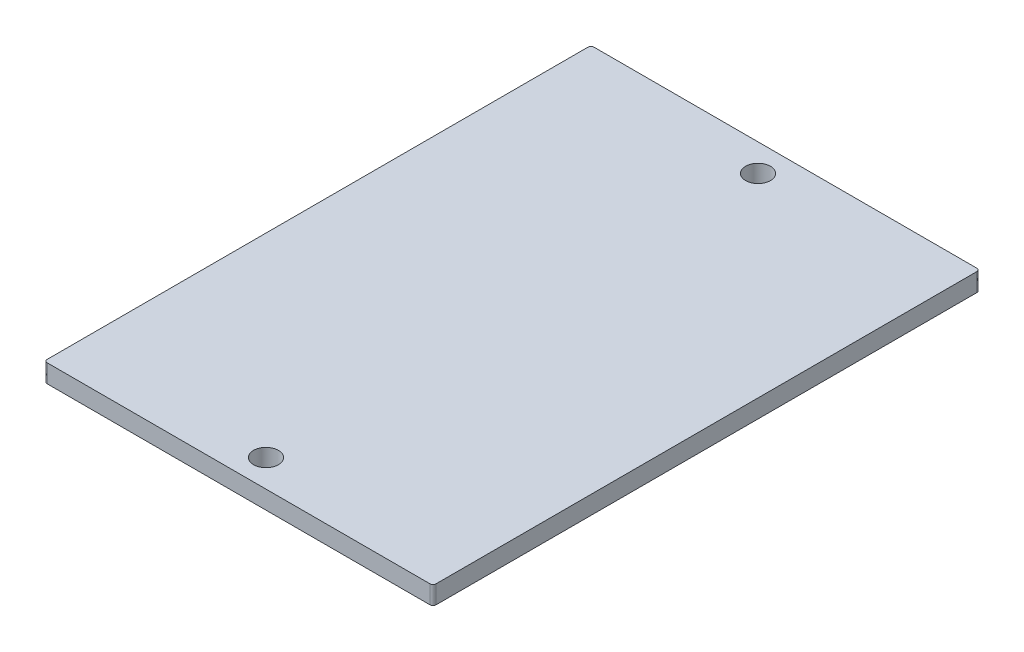
SolidWorks part; units mm, degrees
material "ABS"
ref_plane "Front Plane" through (0, 0, 0) normal (0, 0, 1) x (1, 0, 0)
ref_plane "Top Plane" through (0, 0, 0) normal (0, 1, 0) x (1, 0, 0)
ref_plane "Right Plane" through (0, 0, 0) normal (1, 0, 0) x (0, 0, -1)
sketch "Sketch1" plane through (0, 0, 0) normal (0, 1, 0) x (1, 0, 0)
  line L1 (0, 0) -> (64, 0)
  line L2 (0, 0) -> (0, -90)
  line L3 (0, -90) -> (64, -90)
  line L4 (64, 0) -> (64, -90)
  circle A0 centre (32, -4.5) radius 2.05
  circle A1 centre (32, -85.5) radius 2.05
  point P9 (32, 0)
  point P10 (32, -90)
  dimension "D3" = 4.1
  dimension "D4" = 4.1
  dimension "D1" = 64
  dimension "D2" = 90
  dimension "D5" = 4.5
  dimension "D6" = 4.5
extrude "Boss-Extrude1" add sketch "Sketch1" along normal blind 3
fillet "Fillet1" radius 0.5 4 edges at (0, 1.5, 90) (64, 1.5, 90) (0, 1.5, 0) (64, 1.5, 0)
equation "\"Depth\"= 90mm"
equation "\"Height\" = 150mm"
equation "\"Width\"= 64mm"
equation "\"D1@Sketch1\"=\"Width\""
equation "\"D2@Sketch1\"=\"Depth\" "
